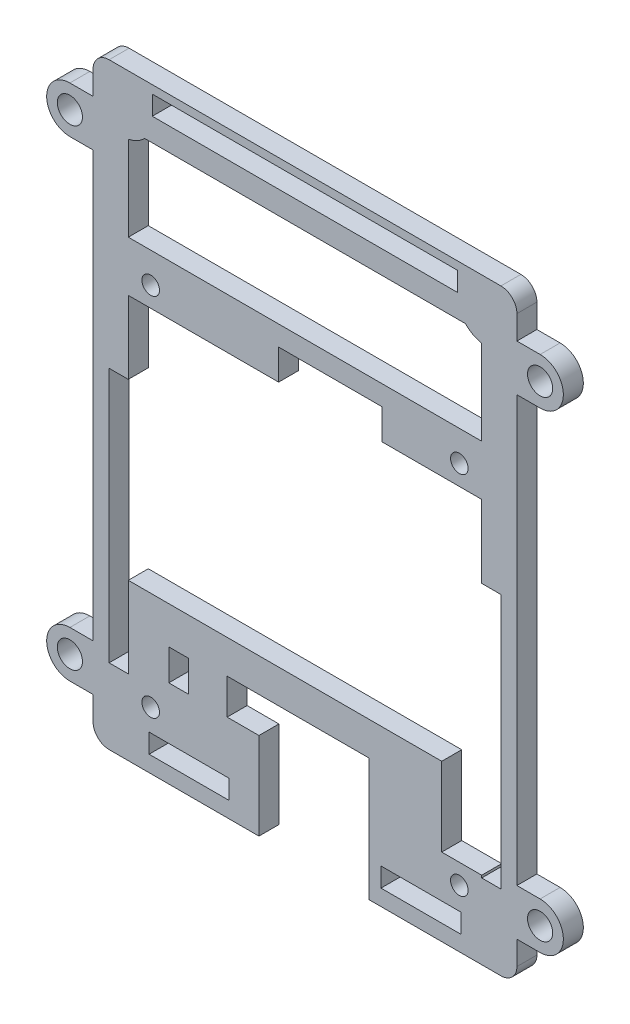
SolidWorks part; units mm, degrees
ref_plane "Front Plane" through (0, 0, 0) normal (0, 0, 1) x (1, 0, 0)
ref_plane "Top Plane" through (0, 0, 0) normal (0, 1, 0) x (1, 0, 0)
ref_plane "Right Plane" through (0, 0, 0) normal (1, 0, 0) x (0, 0, -1)
sketch "Sketch1" plane through (0, 0, 0) normal (0, 0, 1) x (1, 0, 0)
  line L0 (38.227, 0) -> (38.227, 13.8938)
  line L1 (52.832, 0) -> (40.132, 0) construction
  line L2 (38.227, 13.8938) -> (17.907, 13.8938)
  line L3 (17.907, 13.8938) -> (17.907, 8.255)
  line L4 (17.907, 8.255) -> (22.9616, 8.255)
  line L5 (22.9616, 8.255) -> (22.9616, 0)
  line L6 (40.132, 0) -> (16.002, 0) construction
  line L8 (0, 19.2278) -> (49.784, 19.2278)
  line L9 (49.784, 19.2278) -> (49.784, 6.731)
  line L10 (49.784, 6.731) -> (56.134, 6.731)
  line L11 (52.578, 6.731) -> (56.134, 6.731) construction
  line L12 (16.002, 0) -> (3.302, 0) construction
  line L13 (6.4262, 13.2842) -> (9.6012, 13.2842)
  line L14 (6.4262, 13.2842) -> (6.4262, 8.3312)
  line L15 (6.4262, 8.3312) -> (9.6012, 8.3312)
  line L16 (9.6012, 13.2842) -> (9.6012, 8.3312)
  line L17 (0, 6.35) -> (0, -3.048) construction
  line L18 (0, 6.35) -> (0, 46.863) construction
  line L19 (16.002, -3.048) -> (16.002, 0) construction
  line L20 (16.002, -3.048) -> (3.302, -3.048) construction
  line L21 (3.302, -3.048) -> (3.302, 0) construction
  line L22 (40.132, -3.048) -> (40.132, 0) construction
  line L23 (52.832, -3.048) -> (40.132, -3.048) construction
  line L24 (52.832, -3.048) -> (52.832, 0) construction
  line L25 (59.182, 6.35) -> (56.134, 6.35) construction
  line L28 (59.182, 46.863) -> (56.134, 46.863) construction
  line L29 (-3.048, 46.863) -> (0, 46.863) construction
  line L30 (-3.048, 6.35) -> (-3.048, 46.863) construction
  line L31 (-3.048, 6.35) -> (0, 6.35) construction
  line L32 (16.002, -3.048) -> (16.002, 0)
  line L33 (16.002, -3.048) -> (3.302, -3.048)
  line L34 (3.302, -3.048) -> (3.302, 0)
  line L35 (16.002, 0) -> (3.302, 0)
  line L36 (40.132, -3.048) -> (40.132, 0)
  line L37 (52.832, -3.048) -> (40.132, -3.048)
  line L38 (52.832, 0) -> (40.132, 0)
  line L39 (52.832, -3.048) -> (52.832, 0)
  line L40 (59.182, 6.35) -> (56.134, 6.35)
  line L41 (59.182, 46.863) -> (59.182, 6.35)
  line L42 (56.134, 46.863) -> (56.134, 6.35)
  line L43 (59.182, 46.863) -> (56.134, 46.863)
  line L44 (-3.048, 46.863) -> (0, 46.863)
  line L45 (0, 6.35) -> (0, 46.863)
  line L46 (-3.048, 6.35) -> (-3.048, 46.863)
  line L47 (-3.048, 6.35) -> (0, 6.35)
  line L48 (59.182, -5.588) -> (-3.048, -5.588) construction
  line L49 (59.182, -5.588) -> (-3.048, -5.588)
  line L50 (-5.588, -3.048) -> (-5.588, 86.7664)
  line L51 (61.722, -3.048) -> (61.722, 86.7664)
  line L52 (0, 66.421) -> (56.134, 66.421)
  line L53 (3.556, 58.42) -> (0, 58.42) construction
  line L54 (52.578, 58.42) -> (56.134, 58.42) construction
  line L55 (3.556, 58.42) -> (0, 58.42)
  line L56 (52.578, 58.42) -> (56.134, 58.42)
  line L57 (3.556, 58.42) -> (23.876, 58.42)
  line L58 (23.876, 58.42) -> (23.876, 63.246)
  line L59 (23.876, 63.246) -> (40.259, 63.246)
  line L60 (40.259, 63.246) -> (40.259, 58.42)
  line L61 (40.259, 58.42) -> (52.578, 58.42)
  line L63 (-3.048, 89.3064) -> (59.182, 89.3064)
  line L64 (0, 83.2104) -> (56.134, 83.2104)
  line L67 (0, 46.863) -> (0, 83.2104)
  line L68 (56.134, 83.2104) -> (56.134, 46.863)
  line L69 (0, 83.2104) -> (0, 46.863)
  line L70 (3.81, 86.7664) -> (52.324, 86.7664)
  line L71 (3.81, 86.7664) -> (3.81, 84.963)
  line L72 (3.81, 84.963) -> (52.324, 84.963)
  line L73 (52.324, 86.7664) -> (52.324, 84.963)
  line L74 (56.134, 83.2104) -> (56.134, 46.863)
  line L76 (38.227, 0) -> (38.227, -5.588)
  line L77 (22.9616, 0) -> (22.9616, -5.588)
  circle A0 centre (3.556, 3.556) radius 1.397 construction
  circle A1 centre (52.578, 3.556) radius 1.397 construction
  circle A2 centre (3.556, 61.595) radius 1.397 construction
  circle A3 centre (52.578, 61.595) radius 1.397 construction
  circle A4 centre (3.556, 3.556) radius 1.397
  circle A5 centre (52.578, 3.556) radius 1.397
  circle A6 centre (3.556, 61.595) radius 1.397
  circle A7 centre (52.578, 61.595) radius 1.397
  arc A8 (-5.588, -3.048) -> (-3.048, -5.588) centre (-3.048, -3.048) ccw construction
  arc A9 (59.182, -5.588) -> (61.722, -3.048) centre (59.182, -3.048) ccw construction
  arc A10 (-5.588, -3.048) -> (-3.048, -5.588) centre (-3.048, -3.048) ccw
  arc A11 (59.182, -5.588) -> (61.722, -3.048) centre (59.182, -3.048) ccw
  arc A12 (59.182, 89.3064) -> (61.722, 86.7664) centre (59.182, 86.7664) cw
  arc A13 (-5.588, 86.7664) -> (-3.048, 89.3064) centre (-3.048, 86.7664) cw
  point P74 (-5.588, 89.3064)
  dimension "D12" = 3.429
  dimension "D17" = 2.54
  dimension "D1" = 20.32
  dimension "D3" = 15.2654
  dimension "D4" = 8.255
  dimension "D5" = 19.4818
  dimension "D6" = 5.334
  dimension "D7" = 3.175
  dimension "D8" = 4.953
  dimension "D9" = 8.3312
  dimension "D10" = 6.4262
  dimension "D11" = 6.35
  dimension "D13" = 23.495
  dimension "D14" = 23.876
  dimension "D15" = 3.175
  dimension "D16" = 1.8034
  dimension "D18" = 3.556
  dimension "D19" = 3.81
  dimension "D20" = 3.81
  dimension "D21" = 15.875
  dimension "D22" = 16.7894
extrude "Boss-Extrude1" add sketch "Sketch1" along normal blind 3.175 contours L60 L61 L56 L52 L45 L55 L57 L58 L59 A7 A6 | A13 L50 A10 L49 A11 L51 A12 L63 A5 A4 L70 L73 L72 L71 L13 L16 L15 L14 L35 L32 L33 L34 L39 L37 L36 L38 L40 L10 L9 L8 L45 L47 region at (39.3904, 6.9469, 0) region at (0.567, 62.4205, 0)
sketch "Sketch2" plane through (0, 0, 3.175) normal (0, 0, 1) x (1, 0, 0)
  line L0 (-5.588, -3.048) -> (-5.588, 86.7664) construction
  line L1 (-3.048, 89.3064) -> (59.182, 89.3064) construction
  line L2 (61.722, -3.048) -> (61.722, 86.7664) construction
  line L3 (0, 81.3054) -> (56.134, 81.3054)
  line L4 (0, 66.421) -> (0, 83.2104) construction
  line L5 (56.134, 83.2104) -> (56.134, 66.421) construction
  line L6 (0, 79.9092) -> (0, 83.2104)
  line L7 (0, 83.2104) -> (56.134, 83.2104)
  line L8 (56.134, 83.2104) -> (56.134, 79.9092)
  circle A0 centre (-0.8509, 84.5693) radius 4.7371
  circle A1 centre (56.9849, 84.5693) radius 4.7371
  dimension "D1" = 9.4742
  dimension "D2" = 8.001
extrude "Boss-Extrude2" add sketch "Sketch2" against normal up to vertex (3.175 mm away) contours L3 A0 L7 L6 | L6 A0 L3 | A1 L7 A0 L3 | L7 A1 L3 L8 | L3 A1 L8 region at (1.6331, 82.3113, 3.175) region at (0.9571, 80.7762, 3.175) region at (28.067, 82.2509, 3.175) region at (54.5009, 82.3113, 3.175) region at (55.1769, 80.7762, 3.175) up to point (0, 83.2104, 0)
sketch "Sketch3" plane through (0, 0, 3.175) normal (0, 0, 1) x (1, 0, 0)
  line L0 (20.7518, 8.255) -> (20.7518, -5.588)
  line L3 (17.907, 8.255) -> (22.9616, 8.255) construction
  line L4 (22.9616, -5.588) -> (-3.048, -5.588) construction
  line L5 (17.907, 13.8938) -> (15.6972, 13.8938)
  line L6 (15.6972, 13.8938) -> (15.6972, 8.255)
  line L7 (15.6972, 8.255) -> (17.907, 8.255)
  line L8 (17.907, 13.8938) -> (17.907, 8.255)
  line L9 (20.7518, 8.255) -> (22.9616, 8.255)
  line L10 (22.9616, 8.255) -> (22.9616, -5.588)
  line L11 (22.9616, -5.588) -> (20.7518, -5.588)
  dimension "D1" = 2.2098
  dimension "D2" = 2.2098
extrude "Cut-Extrude1" cut sketch "Sketch3" against normal through all
sketch "Sketch4" plane through (0, 0, 3.175) normal (0, 0, 1) x (1, 0, 0)
  line B0 (6.4923, 13.2132) -> (9.6673, 13.2132)
  line B1 (6.4923, 13.2132) -> (6.4923, 8.2602)
  line B2 (9.6673, 13.2132) -> (9.6673, 8.2602)
  line B3 (6.4923, 8.2602) -> (9.6673, 8.2602)
  line B4 (15.7369, 13.9566) -> (15.7369, 8.184)
  line B5 (15.7369, 8.184) -> (20.781, 8.184)
  line B6 (38.329, 13.9566) -> (15.7369, 13.9566)
  line B7 (38.329, -5.5096) -> (38.329, 13.9566)
  line B8 (20.781, 8.184) -> (20.781, -5.5096)
  circle B9 centre (3.6221, 3.485) radius 1.397
  circle B10 centre (52.6441, 3.485) radius 1.397
sketch_block_instance "Block2-1"
sketch_block "Block2"
sketch "Sketch6" plane through (0, 0, 3.175) normal (0, 0, 1) x (1, 0, 0)
  line L1 (3.81, 84.963) -> (52.324, 84.963)
  line L2 (3.81, 84.963) -> (3.81, 88.011)
  line L3 (3.81, 88.011) -> (52.324, 88.011)
  line L4 (52.324, 84.963) -> (52.324, 88.011)
extrude "Cut-Extrude2" cut sketch "Sketch6" against normal through all
sketch "Sketch7" plane through (0, 0, 3.175) normal (0, 0, 1) x (1, 0, 0)
  line L0 (16.002, -3.048) -> (16.002, 0) construction
  line L1 (3.81, 84.963) -> (52.324, 84.963)
  line L2 (3.81, 84.963) -> (3.81, 88.011)
  line L3 (3.81, 88.011) -> (52.324, 88.011)
  line L4 (52.324, 84.963) -> (52.324, 88.011)
  line L5 (3.302, 0) -> (16.002, 0)
  line L6 (3.302, 0) -> (3.302, -3.175)
  line L7 (3.302, -3.175) -> (16.002, -3.175)
  line L8 (16.002, 0) -> (16.002, -3.175)
  line L9 (40.132, 0) -> (52.832, 0)
  line L10 (40.132, 0) -> (40.132, -3.175)
  line L11 (40.132, -3.175) -> (52.832, -3.175)
  line L12 (52.832, 0) -> (52.832, -3.175)
  line L13 (52.832, -3.048) -> (52.832, 0) construction
  line L14 (15.6972, 13.8938) -> (15.6972, 19.2278)
  line L15 (0, 19.2278) -> (49.784, 19.2278) construction
  line L16 (38.227, 13.8938) -> (38.227, 19.2278)
  line L17 (15.6972, 16.5608) -> (38.227, 16.5608)
  line L18 (38.227, 13.8938) -> (15.6972, 13.8938)
  line L19 (10.287, 0) -> (45.847, 0) construction
  line L20 (20.7518, 8.255) -> (18.2118, 8.255)
  line L21 (20.7518, 8.255) -> (20.7518, 0)
  line L22 (20.7518, 0) -> (18.2118, 0)
  line L23 (18.2118, 8.255) -> (18.2118, 0)
  line L38 (10.6012, 7.3312) -> (10.6012, 14.2842)
  line L39 (5.4262, 14.2842) -> (5.4262, 7.3312)
  line L40 (5.4262, 7.3312) -> (10.6012, 7.3312)
  line L41 (10.6012, 14.2842) -> (5.4262, 14.2842)
  line L42 (10.6012, 7.3312) -> (10.6012, 14.2842)
  line L43 (5.4262, 14.2842) -> (5.4262, 7.3312)
  line L44 (5.4262, 7.3312) -> (10.6012, 7.3312)
  line L45 (10.6012, 14.2842) -> (5.4262, 14.2842)
  dimension "D1" = 3.048
  dimension "D2" = 3.175
  dimension "D3" = 2.54
  dimension "D4" = 1
extrude "Cut-Extrude3" [suppressed] cut sketch "Sketch7" against normal through all contours L8 L5 L6 L7 | L12 L9 L10 L11 | L18 L16 L17 L14 | L20 L23 L22 L21 | L42 L45 L43 L44
sketch "Sketch5" plane through (0, 0, 3.175) normal (0, 0, 1) x (1, 0, 0)
  line L0 (-9.2771, 4.4135) -> (65.4111, 4.4135) construction
  line L1 (65.4111, 4.4135) -> (65.4111, 79.3049) construction
  line L2 (65.4111, 79.3049) -> (-9.2771, 79.3049) construction
  line L3 (-9.2771, 79.3049) -> (-9.2771, 4.4135) construction
  line L4 (-9.2771, 41.8592) -> (-5.588, 41.8592) construction
  line L5 (-5.588, -3.048) -> (-5.588, 86.7664) construction
  line L6 (61.722, 41.8592) -> (65.4111, 41.8592) construction
  line L7 (61.722, -3.048) -> (61.722, 86.7664) construction
  line L8 (-9.2771, 82.994) -> (-5.588, 82.994)
  line L9 (-9.2771, 75.6158) -> (-5.588, 75.6158)
  line L10 (-9.2771, 8.1026) -> (-5.588, 8.1026)
  line L11 (-9.2771, 0.7244) -> (-5.588, 0.7244)
  line L12 (65.4111, 0.7244) -> (61.722, 0.7244)
  line L13 (65.4111, 75.6158) -> (61.722, 75.6158)
  line L14 (65.4111, 8.1026) -> (61.722, 8.1026)
  line L15 (65.4111, 82.994) -> (61.722, 82.994)
  line L16 (-5.588, 82.994) -> (-5.588, 75.6158)
  line L17 (61.722, 82.994) -> (61.722, 75.6158)
  line L19 (61.722, 0.7244) -> (61.722, 8.1026)
  line L20 (-5.588, 8.1026) -> (-5.588, 0.7244)
  circle A0 centre (65.4111, 79.3049) radius 2
  circle A1 centre (65.4111, 4.4135) radius 2
  circle A2 centre (-9.2771, 4.4135) radius 2
  circle A3 centre (-9.2771, 79.3049) radius 2
  circle A4 centre (-9.2771, 4.4135) radius 3.6891
  circle A5 centre (-9.2771, 79.3049) radius 3.6891
  circle A6 centre (65.4111, 79.3049) radius 3.6891
  circle A7 centre (65.4111, 4.4135) radius 3.6891
  dimension "D1" = 70.6882
  dimension "D2" = 70.8914
  dimension "D3" = 4
extrude "Boss-Extrude3" add sketch "Sketch5" against normal up to vertex (3.175 mm away) contours A4 L20 L10 | A4 L11 L20 | A4 A2 | A7 A1 | A7 L19 L12 | A7 L14 L19 | A6 A0 | A6 L17 L13 | A6 L15 L17 | A5 L9 L16 | A5 A3 | A5 L16 L8 region at (-6.412, 82.17, 3.175) region at (-6.7423, 81.8397, 3.175) region at (-6.412, 76.4398, 3.175) region at (-6.412, 7.2786, 3.175) region at (-6.7423, 6.9483, 3.175) region at (-6.412, 1.5484, 3.175) region at (62.8763, 1.8787, 3.175) region at (62.546, 1.5484, 3.175) region at (62.546, 7.2786, 3.175) region at (62.8763, 76.7701, 3.175) region at (62.546, 76.4398, 3.175) region at (62.546, 82.17, 3.175) up to point (-5.588, 86.7664, 0)
